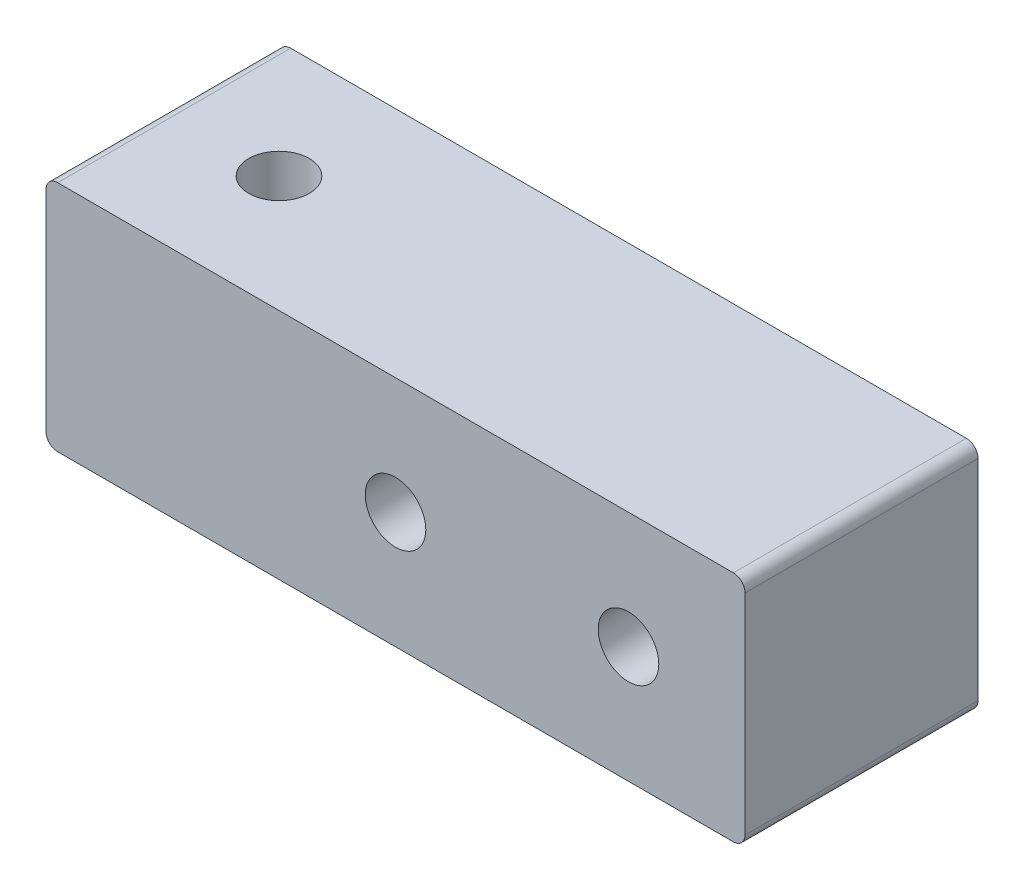
SolidWorks part; units mm, degrees
material "MC901"
ref_plane "正面" through (0, 0, 0) normal (0, 0, 1) x (1, 0, 0)
ref_plane "平面" through (0, 0, 0) normal (0, 1, 0) x (1, 0, 0)
ref_plane "右側面" through (0, 0, 0) normal (1, 0, 0) x (0, 0, -1)
sketch "ｽｹｯﾁ1" plane through (0, 0, 0) normal (0, 0, 1) x (1, 0, 0)
  line L1 (0, 0) -> (30, 0)
  line L2 (0, 0) -> (0, 10)
  line L3 (0, 10) -> (30, 10)
  line L4 (30, 0) -> (30, 10)
  dimension "D1" = 30
  dimension "D2" = 10
extrude "ﾎﾞｽ - 押し出し1" add sketch "ｽｹｯﾁ1" along normal blind 10
sketch "ｽｹｯﾁ2" plane through (0, 10, 0) normal (0, 1, 0) x (1, 0, 0)
  line L0 (0, -5) -> (5, -5) construction
  line L1 (0, -10) -> (0, 0) construction
  circle A0 centre (5, -5) radius 1.3
  dimension "D1" = 2.6
  dimension "D2" = 5
extrude "ｶｯﾄ - 押し出し1" cut sketch "ｽｹｯﾁ2" against normal through all
sketch "ｽｹｯﾁ3" plane through (0, 0, 10) normal (0, 0, 1) x (1, 0, 0)
  line L0 (30, 5) -> (15, 5) construction
  line L1 (30, 0) -> (30, 10) construction
  circle A0 centre (15, 5) radius 1.3
  circle A1 centre (25, 5) radius 1.3
  dimension "D1" = 2.6
  dimension "D2" = 5
  dimension "D3" = 10
extrude "ｶｯﾄ - 押し出し2" cut sketch "ｽｹｯﾁ3" against normal through all
fillet "ﾌｨﾚｯﾄ1" radius 0.5 4 edges at (30, 0, 5) (0, 0, 5) (30, 10, 5) (0, 10, 5)
